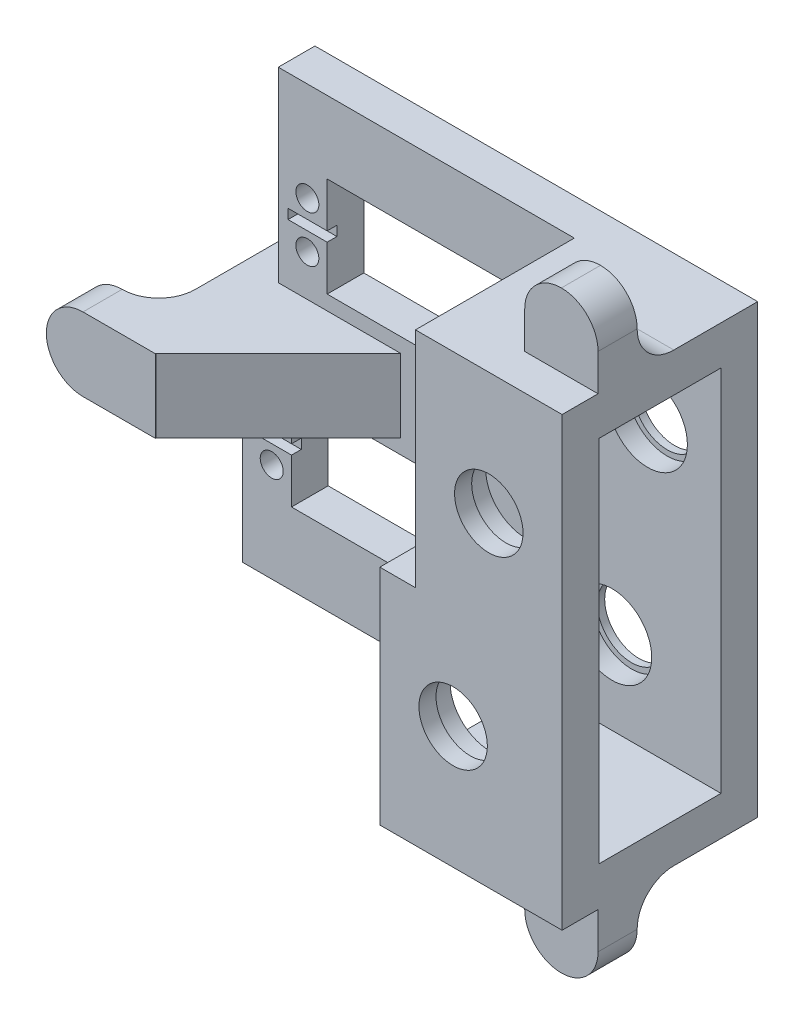
SolidWorks part; units mm, degrees
ref_plane "Front Plane" through (0, 0, 0) normal (0, 0, 1) x (1, 0, 0)
ref_plane "Top Plane" through (0, 0, 0) normal (0, 1, 0) x (1, 0, 0)
ref_plane "Right Plane" through (0, 0, 0) normal (1, 0, 0) x (0, 0, -1)
sketch "Sketch1" plane through (0, 0, 0) normal (0, 0, 1) x (1, 0, 0)
  line L0 (-15, 0) -> (22.2932, 0)
  line L5 (-15, 91.3619) -> (22.2932, 91.3619)
  line L6 (-15, 0) -> (-15, 91.3619)
  line L7 (22.2932, 0) -> (22.2932, 91.3619)
  line L8 (0, 25) -> (7.2932, 66.3619) construction
  line L9 (0, 25) -> (0, 79.2) construction
  circle A1 centre (0, 25) radius 8.125
  circle A2 centre (7.2932, 66.3619) radius 8.125
  point P4 (0, 0)
  dimension "D2" = 16.25
  dimension "D5" = 25
  dimension "D4" = 15
  dimension "D6" = 25
  dimension "D8" = 42
  dimension "D9" = 10
  dimension "D10" = 15
extrude "Boss-Extrude1" add sketch "Sketch1" along normal blind 40
ref_plane "INNER WALL" through (0, 0, 39) normal (0, 0, 1) x (1, 0, 0)
ref_plane "OUTER WALL" through (0, 0, 32.65) normal (0, 0, 1) x (1, 0, 0)
sketch "Sketch2" plane through (0, 0, 0) normal (0, 1, 0) x (1, 0, 0)
  line L1 (-15, -7.5) -> (22.2932, -7.5)
  line L2 (-15, -7.5) -> (-15, -32.5)
  line L3 (-15, -32.5) -> (22.2932, -32.5)
  line L4 (22.2932, -7.5) -> (22.2932, -32.5)
  line L6 (-15, -40) -> (-15, 0) construction
  line L7 (22.2932, -40) -> (22.2932, 0) construction
  point P9 (22.2932, -20)
  point P10 (22.2932, -20)
  dimension "D1" = 25
extrude "Cut-Extrude1" cut sketch "Sketch2" along normal through all from offset 8
sketch "Sketch10" plane through (0, 0, 40) normal (0, 0, 1) x (1, 0, 0)
  circle A0 centre (7.2932, 66.3619) radius 8.125
  circle A1 centre (0, 25) radius 10.837
  circle A2 centre (7.2932, 66.3619) radius 7
  circle A3 centre (0, 25) radius 7
  circle A4 centre (7.2932, 66.3619) radius 8.125 construction
  circle A5 centre (0, 25) radius 8.125 construction
  dimension "D2" = 14
  dimension "D4" = 14
extrude "Boss-Extrude2" add sketch "Sketch10" against normal offset from surface (3.5 mm away) 4 up to face at (-8.125, 25, 32.5)
sketch "Sketch11" plane through (0, 0, 0) normal (0, 0, -1) x (-1, 0, 0)
  circle A0 centre (-7.2932, 66.3619) radius 8.125
  circle A1 centre (-7.2932, 66.3619) radius 7
  circle A2 centre (0, 25) radius 8.125
  circle A3 centre (0, 25) radius 7
  circle A4 centre (0, 25) radius 8.125 construction
  circle A5 centre (-7.2932, 66.3619) radius 8.125 construction
  dimension "D1" = 14
  dimension "D2" = 14
extrude "Boss-Extrude3" add sketch "Sketch11" against normal offset from surface (3.5 mm away) 4 up to face at (8.125, 25, 7.5)
ref_axis "Axis1" through (0, 25, 3.5) along (0, 0, -1)
ref_plane "Plane1" through (0, 25, 0) normal (0, -1, 0) x (-1, 0, 0)
ref_axis "Axis2" through (7.2932, 66.3619, 3.5) along (0, 0, -1)
ref_plane "Plane2" through (0, 66.3619, 0) normal (0, -1, 0) x (-1, 0, 0)
sketch "Sketch12" plane through (0, 0, 0) normal (0, 0, -1) x (-1, 0, 0)
  line L0 (-20.5113, 25) -> (20.5113, 25) construction
  line L1 (15, 0) -> (75.56, 0)
  line L2 (15, 0) -> (15, 91.3619)
  line L3 (15, 91.3619) -> (68.2668, 91.3619)
  line L5 (-20.5113, 66.3619) -> (20.5113, 66.3619) construction
  line L6 (24.66, 35.2) -> (65.56, 35.2)
  line L7 (24.66, 35.2) -> (24.66, 14.8)
  line L8 (24.66, 14.8) -> (65.56, 14.8)
  line L9 (65.56, 35.2) -> (65.56, 14.8)
  line L10 (-22.2932, 91.3619) -> (15, 91.3619) construction
  line L11 (17.3668, 76.5619) -> (58.2668, 76.5619)
  line L12 (17.3668, 76.5619) -> (17.3668, 56.1619)
  line L13 (17.3668, 56.1619) -> (58.2668, 56.1619)
  line L14 (58.2668, 76.5619) -> (58.2668, 56.1619)
  line L16 (15, 0) -> (-22.2932, 0) construction
  line L17 (15, 91.3619) -> (15, 0) construction
  line L18 (68.2668, 91.3619) -> (68.2668, 45.681)
  line L19 (68.2668, 45.681) -> (75.56, 45.681)
  line L20 (75.56, 45.681) -> (75.56, 0)
  line L21 (58.2668, 56.1619) -> (58.2668, 35.2) construction
  line L22 (45.11, 35.2) -> (45.11, 14.8) construction
  line L32 (37.8168, 76.5619) -> (37.8168, 56.1619) construction
  circle A0 centre (35, 25) radius 6.6 construction
  circle A1 centre (0, 25) radius 7 construction
  circle A2 centre (27.7068, 66.3619) radius 6.6 construction
  circle A3 centre (-7.2932, 66.3619) radius 7 construction
  point P15 (45.11, 14.8)
  point P16 (65.56, 26)
  point P17 (58.2668, 45.681)
  point P24 (24.66, 15.2353)
  point P27 (17.3668, 66.3619)
  point P34 (37.8168, 56.1619)
  point P53 (45.11, 25)
  dimension "D7" = 13.2
  dimension "D11" = 13.2
  dimension "D2" = 20.4
  dimension "D3" = 40.9
  dimension "D4" = 10.11
  dimension "D9" = 10.11
  dimension "D5" = 35
  dimension "D6" = 10
  dimension "D8" = 10
extrude "Boss-Extrude4" add sketch "Sketch12" against normal up to surface (7.5 mm away) up to face at (8.125, 25, 7.5)
sketch "Sketch13" plane through (0, 0, 0) normal (0, 0, -1) x (-1, 0, 0)
  line L0 (24.66, 35.2) -> (24.66, 14.8) construction
  line L1 (-20.5113, 25) -> (20.5113, 25) construction
  line L2 (65.56, 14.8) -> (65.56, 35.2) construction
  line L3 (17.3668, 76.5619) -> (17.3668, 56.1619) construction
  line L5 (-20.5113, 66.3619) -> (20.5113, 66.3619) construction
  line L6 (58.2668, 56.1619) -> (58.2668, 76.5619) construction
  circle A0 centre (20.61, 29.75) radius 2.3495
  circle A1 centre (20.61, 20.25) radius 2.3495
  circle A2 centre (69.61, 29.75) radius 2.3495
  circle A3 centre (69.61, 20.25) radius 2.3495
  circle A4 centre (13.3168, 71.1119) radius 2.3495
  circle A5 centre (13.3168, 61.6119) radius 2.3495
  circle A6 centre (62.3168, 71.1119) radius 2.3495
  circle A7 centre (62.3168, 61.6119) radius 2.3495
  dimension "D1" = 4.699
  dimension "D2" = 4.05
  dimension "D3" = 9.5
  dimension "D4" = 4.75
  dimension "D5" = 4.05
  dimension "D7" = 9.5
  dimension "D8" = 4.05
  dimension "D9" = 4.75
  dimension "D10" = 4.05
extrude "Cut-Extrude2" cut sketch "Sketch13" against normal up to next
sketch "Sketch22" plane through (0, 0, 7.5) normal (0, 0, 1) x (1, 0, 0)
  line L0 (-58.2668, 56.1619) -> (-58.2668, 76.5619) construction
  line L1 (-58.2668, 65.3619) -> (-66.2668, 65.3619)
  line L2 (-58.2668, 65.3619) -> (-58.2668, 67.3619)
  line L3 (-58.2668, 67.3619) -> (-66.2668, 67.3619)
  line L4 (-66.2668, 65.3619) -> (-66.2668, 67.3619)
  line L5 (-17.3668, 76.5619) -> (-17.3668, 56.1619) construction
  line L6 (-17.3668, 65.3619) -> (-9.3668, 65.3619)
  line L7 (-17.3668, 65.3619) -> (-17.3668, 67.3619)
  line L8 (-17.3668, 67.3619) -> (-9.3668, 67.3619)
  line L9 (-9.3668, 65.3619) -> (-9.3668, 67.3619)
  line L10 (-24.66, 35.2) -> (-24.66, 14.8) construction
  line L11 (-24.66, 24) -> (-16.66, 24)
  line L12 (-24.66, 24) -> (-24.66, 26)
  line L13 (-24.66, 26) -> (-16.66, 26)
  line L14 (-16.66, 24) -> (-16.66, 26)
  line L15 (-65.56, 14.8) -> (-65.56, 35.2) construction
  line L16 (-65.56, 24) -> (-73.56, 24)
  line L17 (-65.56, 24) -> (-65.56, 26)
  line L18 (-65.56, 26) -> (-73.56, 26)
  line L19 (-73.56, 24) -> (-73.56, 26)
  point P24 (-58.2668, 66.3619)
  point P25 (-66.2668, 66.3619)
  point P26 (-73.56, 25)
  point P27 (-65.56, 25)
  point P28 (-65.56, 24)
  dimension "D1" = 2
  dimension "D2" = 8
extrude "Cut-Extrude6" cut sketch "Sketch22" against normal blind 2
sketch "Sketch14" plane through (0, 0, 7.5) normal (0, 0, 1) x (1, 0, 0)
  line L0 (22.2932, 0) -> (22.2932, 91.3619) construction
  line L1 (22.2932, 91.3619) -> (-15, 91.3619)
  line L2 (22.2932, 91.3619) -> (22.2932, 83.3619)
  line L3 (22.2932, 83.3619) -> (-15, 83.3619)
  line L4 (-15, 91.3619) -> (-15, 83.3619)
  line L5 (22.2932, 91.3619) -> (-15, 91.3619) construction
  line L6 (-15, 91.3619) -> (-15, 0) construction
  dimension "D1" = 8
extrude "Boss-Extrude5" add sketch "Sketch14" along normal up to surface (25 mm away) up to face at (-8.125, 25, 32.5)
sketch "Sketch18" plane through (0, 0, 40) normal (0, 0, 1) x (1, 0, 0)
  line L0 (7.2932, 66.3619) -> (7.2932, 25) construction
  line L1 (-15, 91.3619) -> (-7.7068, 91.3619)
  line L2 (-15, 91.3619) -> (-15, 45.681)
  line L3 (-15, 45.681) -> (-7.7068, 45.681)
  line L4 (-7.7068, 91.3619) -> (-7.7068, 45.681)
  line L5 (0, 25) -> (7.2932, 25) construction
  circle A0 centre (7.2932, 66.3619) radius 8.125 construction
  point P13 (7.2932, 45.681)
  dimension "D1" = 15
extrude "Cut-Extrude4" cut sketch "Sketch18" against normal up to surface (32.5 mm away) up to face at (-45.11, 25, 7.5)
sketch "Sketch15" plane through (0, 0, 0) normal (0, 0, -1) x (-1, 0, 0)
  circle A0 centre (0, 25) radius 11
  circle A1 centre (-7.2932, 66.3619) radius 11
  dimension "D1" = 22
extrude "Cut-Extrude3" cut sketch "Sketch15" against normal blind 2
sketch "Sketch19" plane through (0, 0, 32.65) normal (0, 0, 1) x (1, 0, 0)
  line L1 (22.2932, 91.3619) -> (7.2932, 91.3619)
  line L2 (22.2932, 91.3619) -> (22.2932, 106.3619)
  line L3 (22.2932, 106.3619) -> (7.2932, 106.3619)
  line L4 (7.2932, 91.3619) -> (7.2932, 106.3619)
  line L5 (22.2932, 0) -> (7.2932, 0)
  line L6 (22.2932, 0) -> (22.2932, -15)
  line L7 (22.2932, -15) -> (7.2932, -15)
  line L8 (7.2932, 0) -> (7.2932, -15)
  line L9 (-15, 0) -> (22.2932, 0) construction
  point P10 (2.4653, 91.3619)
  point P12 (0, 0)
  point P13 (0, 0)
  point P14 (0, 0)
  point P15 (0, 0)
  point P16 (0, 0)
  point P17 (6.7426, 0)
  dimension "D1" = 15
  dimension "D2" = 15
extrude "Boss-Extrude6" add sketch "Sketch19" against normal blind 8
sketch "Sketch20" plane through (0, 0, 32.65) normal (0, 0, 1) x (1, 0, 0)
  line L0 (-15, 45.681) -> (-7.7068, 45.681) construction
  line L1 (-90.56, 38.181) -> (-68.2668, 38.181)
  line L2 (-90.56, 38.181) -> (-90.56, 53.181)
  line L3 (-90.56, 53.181) -> (-68.2668, 53.181)
  line L4 (-68.2668, 38.181) -> (-68.2668, 53.181)
  line L5 (-75.56, 0) -> (-75.56, 45.681) construction
  line L6 (-68.2668, 45.681) -> (-68.2668, 91.3619) construction
  point P4 (-68.2668, 45.681)
  dimension "D1" = 15
  dimension "D2" = 15
extrude "Boss-Extrude7" add sketch "Sketch20" against normal blind 8 separate body
sketch "Sketch21" plane through (0, 0, 24.65) normal (0, 0, -1) x (-1, 0, 0)
  line L0 (90.56, 38.181) -> (68.2668, 38.181) construction
  line L1 (68.2668, 53.181) -> (75.56, 53.181)
  line L2 (68.2668, 53.181) -> (68.2668, 38.181)
  line L3 (68.2668, 38.181) -> (75.56, 38.181)
  line L4 (75.56, 53.181) -> (75.56, 38.181)
  line L5 (75.56, 0) -> (75.56, 45.681) construction
  point P9 (75.56, 38.181)
extrude "Boss-Extrude8" add sketch "Sketch21" along normal up to surface (24.65 mm away) up to face at (-11, 25, 0)
fillet "Fillet1" radius 7.5 9 edges at (-90.56, 53.181, 28.65) (-90.56, 38.181, 28.65) (-75.56, 45.681, 24.65) (7.2932, 106.3619, 28.65) (22.2932, 106.3619, 28.65) (7.2932, -15, 28.65) (22.2932, -15, 28.65) (14.7932, 0, 24.65) (14.7932, 91.3619, 24.65)
chamfer "Chamfer1" distance 25 angle 45 1 edges at (-68.2668, 45.681, 7.5)
equation "\"D4@Sketch13\"=\"D3@Sketch13\"/2"
equation "\"D5@Sketch12\"=\"D1@Sketch12\""
equation "\"D8@Sketch13\"=\"D2@Sketch13\""
equation "\"D9@Sketch13\"=\"D7@Sketch13\"/2"
equation "\"D10@Sketch13\"=\"D5@Sketch13\""
